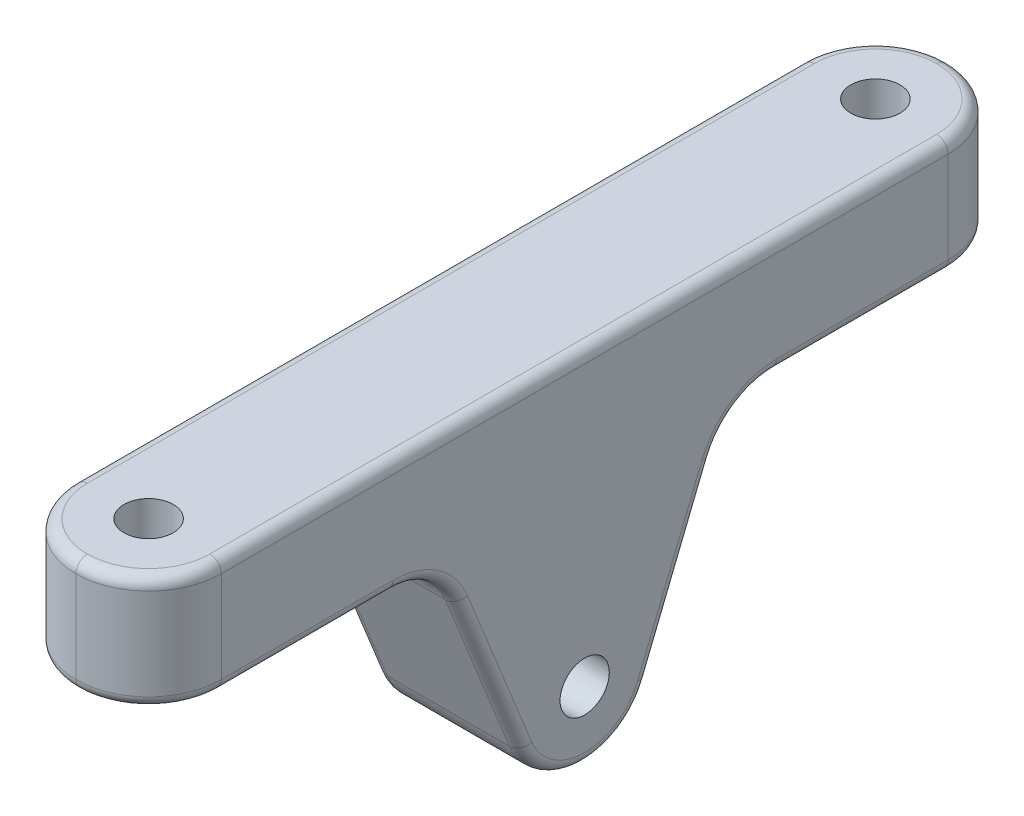
SolidWorks part; units mm, degrees
ref_plane "Front Plane" through (0, 0, 0) normal (0, 0, 1) x (1, 0, 0)
ref_plane "Top Plane" through (0, 0, 0) normal (0, 1, 0) x (1, 0, 0)
ref_plane "Right Plane" through (0, 0, 0) normal (1, 0, 0) x (0, 0, -1)
sketch "Sketch1" plane through (0, 0, 0) normal (1, 0, 0) x (0, 0, -1)
  line L0 (-38.1, 25.4) -> (38.1, 25.4)
  line L1 (-38.1, 25.4) -> (-38.1, 15.4)
  line L2 (-38.1, 15.4) -> (-12.7, 15.4)
  line L3 (-12.7, 15.4) -> (0, -16.0037)
  line L4 (0, -16.0037) -> (12.7, 15.4)
  line L5 (12.7, 15.4) -> (38.1, 15.4)
  line L6 (38.1, 15.4) -> (38.1, 25.4)
  circle A0 centre (0, 0) radius 2.15
  point P14 (0, 25.4)
  dimension "D1" = 4.3
  dimension "D2" = 25.4
  dimension "D3" = 10
  dimension "D4" = 38.1
  dimension "D5" = 6
  dimension "D6" = 25.4
extrude "Boss-Extrude1" add sketch "Sketch1" along normal blind 12.7
fillet "Fillet1" radius 6 3 edges at (6.35, 15.4, -12.7) (6.35, 15.4, 12.7) (6.35, -16.0037, 0)
fillet "Fillet2" radius 6.35 4 edges at (0, 20.4, -38.1) (12.7, 20.4, -38.1) (0, 20.4, 38.1) (12.7, 20.4, 38.1)
sketch "Sketch2" plane through (0, 25.4, 0) normal (0, 1, 0) x (1, 0, 0)
  circle A0 centre (6.35, -31.75) radius 2.15
  circle A1 centre (6.35, 31.75) radius 2.15
  arc A2 (6.35, 38.1) -> (0, 31.75) centre (6.35, 31.75) ccw construction
  arc A3 (6.35, 38.1) -> (0, 31.75) centre (6.35, 31.75) ccw
  arc A4 (0, -31.75) -> (6.35, -38.1) centre (6.35, -31.75) ccw construction
  arc A5 (0, -31.75) -> (6.35, -38.1) centre (6.35, -31.75) ccw
  point P4 (0, 0)
  point P7 (0, 0)
  point P10 (0, 0)
  dimension "D1" = 4.3
extrude "Cut-Extrude1" cut sketch "Sketch2" against normal up to next contours A0 | A1 region at (6.35, 25.4, 31.75) region at (6.35, 25.4, -31.75)
sketch "Sketch3" plane through (0, 0, 0) normal (-1, 0, 0) x (0, 0, 1)
  line L1 (0, 4.7343) -> (-4.1, 2.3671)
  line L2 (-4.1, 2.3671) -> (-4.1, -2.3671)
  line L3 (-4.1, -2.3671) -> (0, -4.7343)
  line L4 (0, -4.7343) -> (4.1, -2.3671)
  line L5 (4.1, -2.3671) -> (4.1, 2.3671)
  line L6 (4.1, 2.3671) -> (0, 4.7343)
  circle A0 centre (0, 0) radius 4.1 construction
  dimension "D1" = 8.2
extrude "Cut-Extrude2" cut sketch "Sketch3" against normal blind 4
fillet "Fillet3" radius 1 24 edges at (10.8401, 25.4, -36.2401) (1.8599, 25.4, -36.2401) (0, 25.4, 0) (1.8599, 25.4, 36.2401) (10.8401, 25.4, 36.2401) (12.7, 14.3748, 13.3913) (12.7, 15.4, 24.2478) (10.8401, 15.4, 36.2401) (1.8599, 15.4, 36.2401) (0, 15.4, 24.2478) (0, 14.3748, 13.3913) (0, 4.7, 8.3728) (0, -6, 0) (0, 4.7, -8.3728) (0, 14.3748, -13.3913) (0, 15.4, -24.2478) (1.8599, 15.4, -36.2401) (10.8401, 15.4, -36.2401) (12.7, 15.4, -24.2478) (12.7, 14.3748, -13.3913) (12.7, 4.7, -8.3728) (12.7, -6, 0) (12.7, 25.4, 0) (12.7, 4.7, 8.3728)
